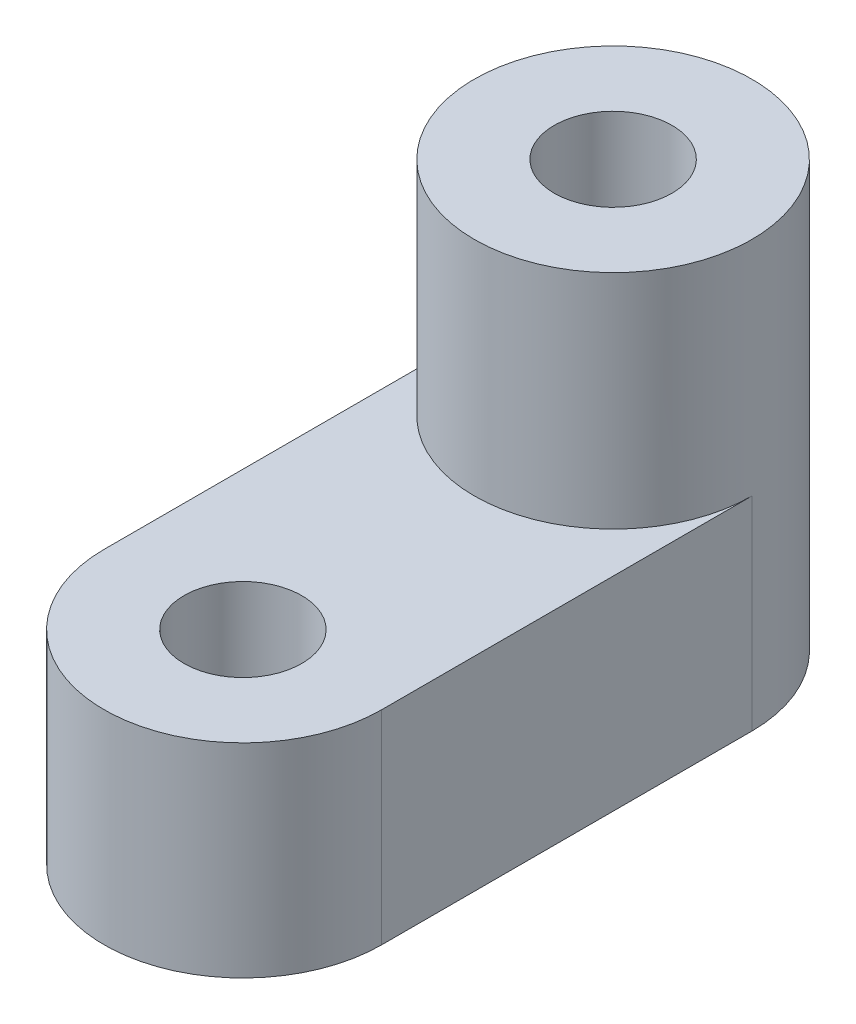
SolidWorks part; units mm, degrees
ref_plane "Front Plane" through (0, 0, 0) normal (0, 0, 1) x (1, 0, 0)
ref_plane "Top Plane" through (0, 0, 0) normal (0, 1, 0) x (1, 0, 0)
ref_plane "Right Plane" through (0, 0, 0) normal (1, 0, 0) x (0, 0, -1)
sketch "Sketch1" plane through (0, 0, 0) normal (0, 1, 0) x (1, 0, 0)
  line L2 (-3.75, 0) -> (-3.75, 10)
  line L3 (-3.75, 10) -> (3.75, 10)
  line L4 (3.75, 0) -> (3.75, 10)
  circle A0 centre (0, 0) radius 3.75
  point P0 (0, 0)
  dimension "D3" = 7.5
  dimension "D1" = 10
  dimension "D2" = 3.75
extrude "Boss-Extrude1" add sketch "Sketch1" along normal blind 5.5 contours A0 L4 L3 L2 | A0 region at (0, 0, -6.423)
sketch "Sketch2" plane through (0, 5.5, 0) normal (0, 1, 0) x (1, 0, 0)
  circle A0 centre (0, 0) radius 1.59
extrude "Cut-Extrude1" cut sketch "Sketch2" against normal through all
sketch "Sketch3" plane through (0, 5.5, 0) normal (0, 1, 0) x (1, 0, 0)
  line L0 (-3.75, 0) -> (-3.75, 10) construction
  circle A0 centre (0, 10) radius 3.75
  dimension "D2" = 7.5
  dimension "D1" = 10
  dimension "D3" = 3.75
extrude "Boss-Extrude2" add sketch "Sketch3" along normal blind 6 and the other way up to surface (5.5 mm away) other way up to face at (0, 0, 1.59)
sketch "Sketch4" plane through (0, 11.5, 0) normal (0, 1, 0) x (1, 0, 0)
  circle A0 centre (0, 10) radius 1.59
extrude "Cut-Extrude2" cut sketch "Sketch4" against normal blind 10
sketch "Sketch6" plane through (0, 5.5, 0) normal (0, 1, 0) x (1, 0, 0)
sketch "Sketch7" plane through (-3.75, 0, 0) normal (-1, 0, 0) x (0, 0, 1)
  line L0 (-10.1052, 5.5) -> (-10.1052, 0)
  line L1 (0, 5.5) -> (-10, 5.5) construction
  line L2 (0, 0) -> (-10, 0) construction
sketch "Sketch8" plane through (3.75, 0, 0) normal (1, 0, 0) x (0, 0, -1)
  line L0 (9.8459, 5.5) -> (9.8459, 0)
  line L1 (0, 5.5) -> (10, 5.5) construction
  line L2 (0, 0) -> (10, 0) construction
